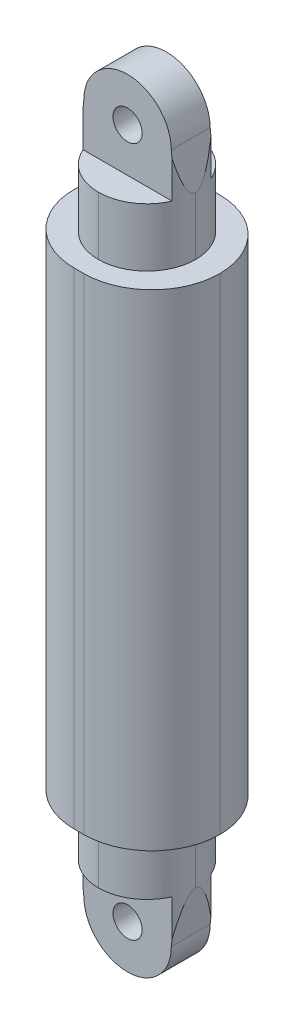
SolidWorks part; units mm, degrees
ref_plane "Front Plane" through (0, 0, 0) normal (0, 0, 1) x (1, 0, 0)
ref_plane "Top Plane" through (0, 0, 0) normal (0, 1, 0) x (1, 0, 0)
ref_plane "Right Plane" through (0, 0, 0) normal (1, 0, 0) x (0, 0, -1)
sketch "Sketch2" plane through (0, 0, 0) normal (0, 0, 1) x (1, 0, 0)
  line L1 (-5, -40) -> (5, -40)
  line L2 (-5, -40) -> (-5, 40)
  line L3 (-5, 40) -> (5, 40)
  line L4 (5, -40) -> (5, 40)
  line L5 (-5, -40) -> (5, 40) construction
  line L6 (-5, 40) -> (5, -40) construction
  point P0 (0, 0)
  dimension "D1" = 80
  dimension "D2" = 10
extrude "Boss-Extrude1" add sketch "Sketch2" along normal blind 10
fillet "Fillet1" radius 5 4 edges at (-5, 0, 0) (5, 0, 0) (5, 0, 10) (-5, 0, 10)
sketch "Sketch3" plane through (0, 0, 0) normal (0, 0, 1) x (1, 0, 0)
  line L0 (-5, -40) -> (-5, 40) construction
  line L1 (5, -40) -> (-5, -40)
  line L2 (5, -40) -> (5, -31)
  line L3 (5, -31) -> (-5, -31)
  line L4 (-5, -40) -> (-5, -31)
  line L5 (0, -40) -> (0, 40) construction
  line L6 (-5, -31) -> (-4.5, -35.5)
  line L7 (5, -31) -> (4.5, -35.5)
  arc A0 (-4.5, -35.5) -> (4.5, -35.5) centre (0, -35.5) ccw
  dimension "D1" = 4.5
  dimension "D2" = 9
  dimension "D3" = 9
extrude "Cut-Extrude1" cut sketch "Sketch3" along normal blind 3 contours L6 A0 L7 L3 | A0 L1 L2 L7 | A0 L6 L4 L1 region at (4.0557, -37.9043, 0) region at (-4.0557, -37.9043, 0) region at (0, -35.0021, 0)
extrude "Cut-Extrude2" cut sketch "Sketch3<2>" along normal blind 3 from offset 7 contours L2 L3 L4 L1
sketch "Sketch3<2>" plane through (0, 0, 0) normal (0, 0, 1) x (1, 0, 0) same geometry as "Sketch3"
mirror "Mirror1" about plane through (0, 0, 0) normal (0, 1, 0) of "Cut-Extrude2", "Cut-Extrude1"
extrude "Cut-Extrude4" cut sketch "Sketch3<4>" against normal blind 4 and the other way through all contours A0 L1 L2 L7 | A0 L6 L4 L1 region at (4.0557, -37.9043, 0) region at (-4.0557, -37.9043, 0)
sketch "Sketch3<4>" plane through (0, 0, 0) normal (0, 0, 1) x (1, 0, 0) same geometry as "Sketch3"
sketch "Sketch7" plane through (0, 0, 3) normal (0, 0, -1) x (-1, 0, 0)
  circle A0 centre (0, -35.5) radius 1.5
  dimension "D1" = 3
extrude "Cut-Extrude5" cut sketch "Sketch7" against normal through all
mirror "Mirror3" about plane through (0, 0, 0) normal (0, 1, 0) of "Cut-Extrude5"
mirror "Mirror4" about plane through (0, 0, 0) normal (0, 1, 0) of "Cut-Extrude4"
ref_plane "Plane1" through (0, 0, 5) normal (0, 0, 1) x (1, 0, 0)
sketch "Sketch9" plane through (0, 0, 5) normal (0, 0, 1) x (1, 0, 0)
  line L0 (-7.5, -25) -> (7.5, -25)
  line L1 (-7.5, -25) -> (-7.5, 25)
  line L2 (-7.5, 25) -> (7.5, 25)
  line L3 (7.5, -25) -> (7.5, 25)
  line L4 (-7.5, -25) -> (7.5, 25) construction
  line L5 (-7.5, 25) -> (7.5, -25) construction
  line L6 (0, 25) -> (0, -25) construction
  point P0 (0, 0)
  dimension "D1" = 50
  dimension "D2" = 15
extrude "Boss-Extrude2" add sketch "Sketch9" along normal blind 7 and the other way blind 7
fillet "Fillet3" radius 7 4 edges at (-7.5, 0, 12) (7.5, 0, 12) (7.5, 0, -2) (-7.5, 0, -2)
